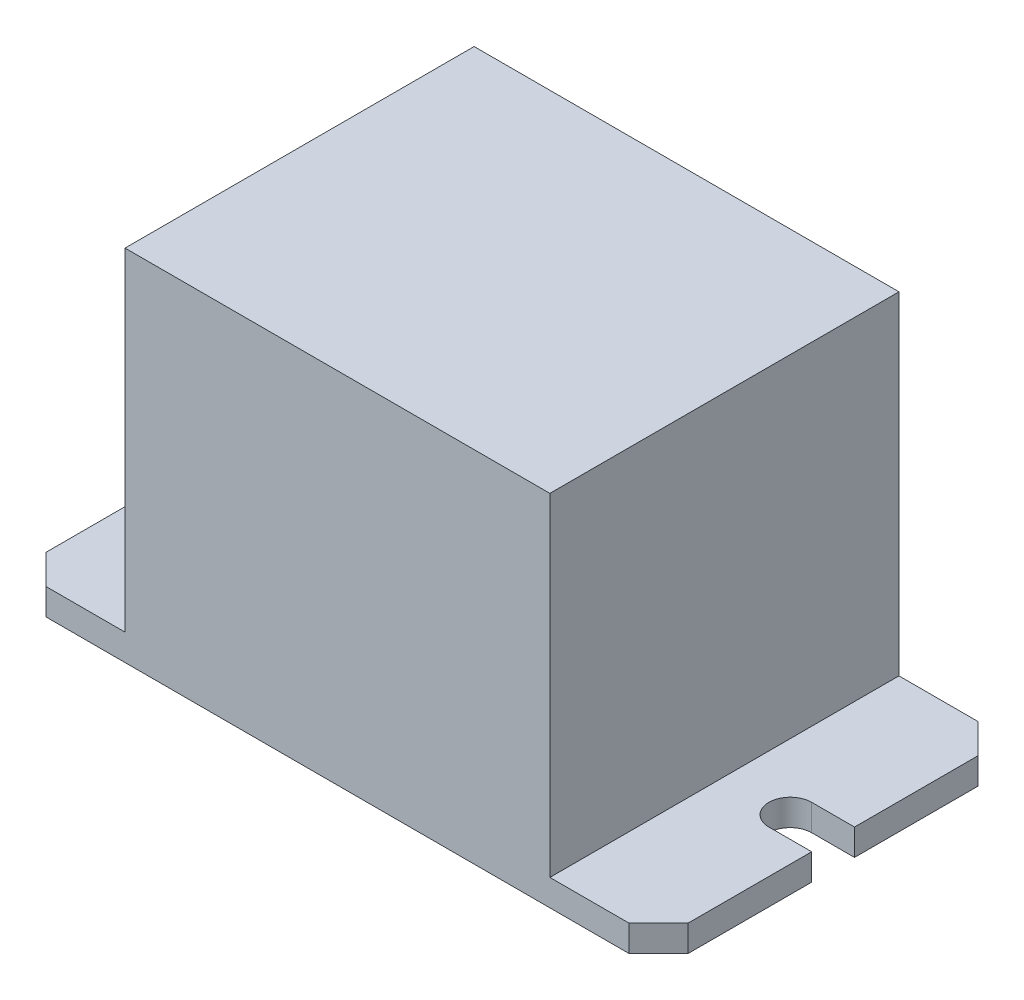
SolidWorks part; units mm, degrees
ref_plane "Front Plane" through (0, 0, 0) normal (0, 0, 1) x (1, 0, 0)
ref_plane "Top Plane" through (0, 0, 0) normal (0, 1, 0) x (1, 0, 0)
ref_plane "Right Plane" through (0, 0, 0) normal (1, 0, 0) x (0, 0, -1)
sketch "Sketch1" plane through (0, 0, 0) normal (0, 1, 0) x (1, 0, 0)
  line L0 (20.8328, -13.5259) -> (14.7368, -13.5259)
  line L1 (-18.0292, 13.3981) -> (14.7368, 13.3981)
  line L2 (-18.0292, 13.3981) -> (-18.0292, -13.5259)
  line L3 (-18.0292, -13.5259) -> (14.7368, -13.5259)
  line L4 (14.7368, 13.3981) -> (14.7368, -13.5259)
  line L8 (23.1188, 11.1121) -> (23.1188, 1.5871)
  line L12 (-26.4112, 11.1121) -> (-26.4112, 1.5871)
  line L13 (-24.1252, -13.5259) -> (-26.4112, -11.2399)
  line L14 (-24.1252, 13.3981) -> (-26.4112, 11.1121)
  line L15 (20.8328, 13.3981) -> (23.1188, 11.1121)
  line L16 (23.1188, -11.2399) -> (20.8328, -13.5259)
  line L17 (14.7368, 13.3981) -> (20.8328, 13.3981)
  line L19 (-24.1252, 13.3981) -> (-18.0292, 13.3981)
  line L20 (-24.1252, -13.5259) -> (-18.0292, -13.5259)
  line L22 (-26.4112, -1.7149) -> (-26.4112, -11.2399)
  line L23 (-23.1092, 1.5871) -> (-26.4112, 1.5871)
  line L24 (-23.1092, -1.7149) -> (-26.4112, -1.7149)
  line L25 (19.8168, 1.5871) -> (23.1188, 1.5871)
  line L26 (19.8168, -1.7149) -> (23.1188, -1.7149)
  line L27 (23.1188, -1.7149) -> (23.1188, -11.2399)
  arc A0 (-23.1092, -1.7149) -> (-23.1092, 1.5871) centre (-23.1092, -0.0639) ccw
  arc A1 (19.8168, 1.5871) -> (19.8168, -1.7149) centre (19.8168, -0.0639) ccw
  dimension "D1" = 26.924
  dimension "D2" = 32.766
extrude "Boss-Extrude1" add sketch "Sketch1" along normal blind 27.686 contours L2 L1 L4 L3
extrude "Boss-Extrude2" add sketch "Sketch1<12>" along normal blind 2.032 contours L24 A0 L23 L12 L14 L19 L2 L20 L13 L22
sketch "Sketch1<12>" plane through (0, 0, 0) normal (0, 1, 0) x (1, 0, 0) same geometry as "Sketch1"
extrude "Boss-Extrude3" add sketch "Sketch1<13>" along normal blind 2.032 contours L25 A1 L26 L27 L16 L0 L4 L17 L15 L8
sketch "Sketch1<13>" plane through (0, 0, 0) normal (0, 1, 0) x (1, 0, 0) same geometry as "Sketch1"
sketch "Sketch2" plane through (0, 27.686, 0) normal (0, 1, 0) x (1, 0, 0)
  circle A0 centre (-13.2287, 8.1905) radius 1.6271
  circle A1 centre (-13.2287, -7.7542) radius 1.8152
  circle A2 centre (-1.2326, -7.7542) radius 1.8338
  circle A3 centre (10.2371, -7.7542) radius 1.3423
